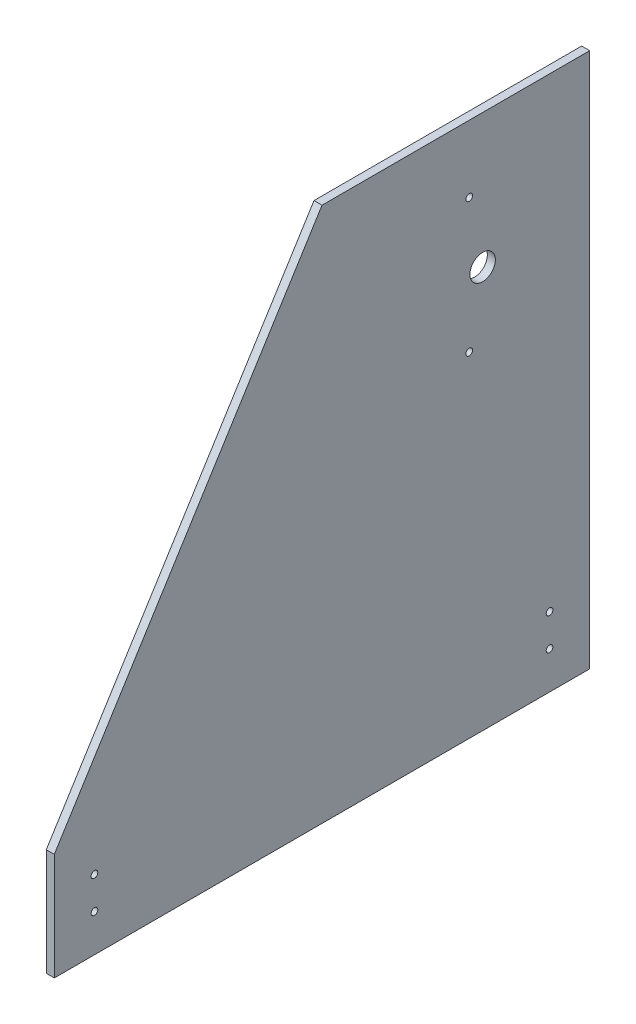
SolidWorks part; units mm, degrees
ref_plane "Front Plane" through (0, 0, 0) normal (0, 0, 1) x (1, 0, 0)
ref_plane "Top Plane" through (0, 0, 0) normal (0, 1, 0) x (1, 0, 0)
ref_plane "Right Plane" through (0, 0, 0) normal (1, 0, 0) x (0, 0, -1)
sketch "Sketch1" plane through (0, 0, 0) normal (1, 0, 0) x (0, 0, -1)
  line L0 (0, -2343.7616) -> (0, 114844.3172) construction
  line L1 (-2343.7616, 0) -> (114844.3172, 0) construction
  line L2 (0, 80) -> (400, 80) construction
  line L3 (0, 0) -> (400, 0)
  line L5 (200, 400) -> (400, 400)
  line L6 (400, 0) -> (400, 400)
  line L7 (0, 80) -> (200, 400)
  line L8 (0, 80) -> (0, 0)
  line L9 (-1000, 40) -> (49000, 40) construction
  line L10 (200, -1000) -> (200, 49000) construction
  line L11 (310, -1000) -> (310, 49000) construction
  line L12 (320, -1008.4066) -> (320, 48991.5934) construction
  line L13 (298.2689, 300) -> (341.7311, 300) construction
  circle A0 centre (30, 52) radius 2.5
  circle A2 centre (30, 28) radius 2.5
  circle A3 centre (370, 28) radius 2.5
  circle A4 centre (370, 52) radius 2.5
  circle A5 centre (310, 350) radius 2.5
  circle A6 centre (310, 250) radius 2.5
  circle A7 centre (320, 300) radius 9.5
  point P14 (0, 40)
  point P21 (200, 0)
  point P38 (320, 300)
  dimension "D7" = 5
  dimension "D9" = 5
  dimension "D14" = 19
  dimension "D1" = 400
  dimension "D2" = 400
  dimension "D3" = 80
  dimension "D4" = 200
  dimension "D5" = 30
  dimension "D6" = 90
  dimension "D8" = 12
  dimension "D10" = 50
  dimension "D11" = 100
  dimension "D12" = 80
  dimension "D13" = 50
extrude "Boss-Extrude1" add sketch "Sketch1" along normal blind 6
